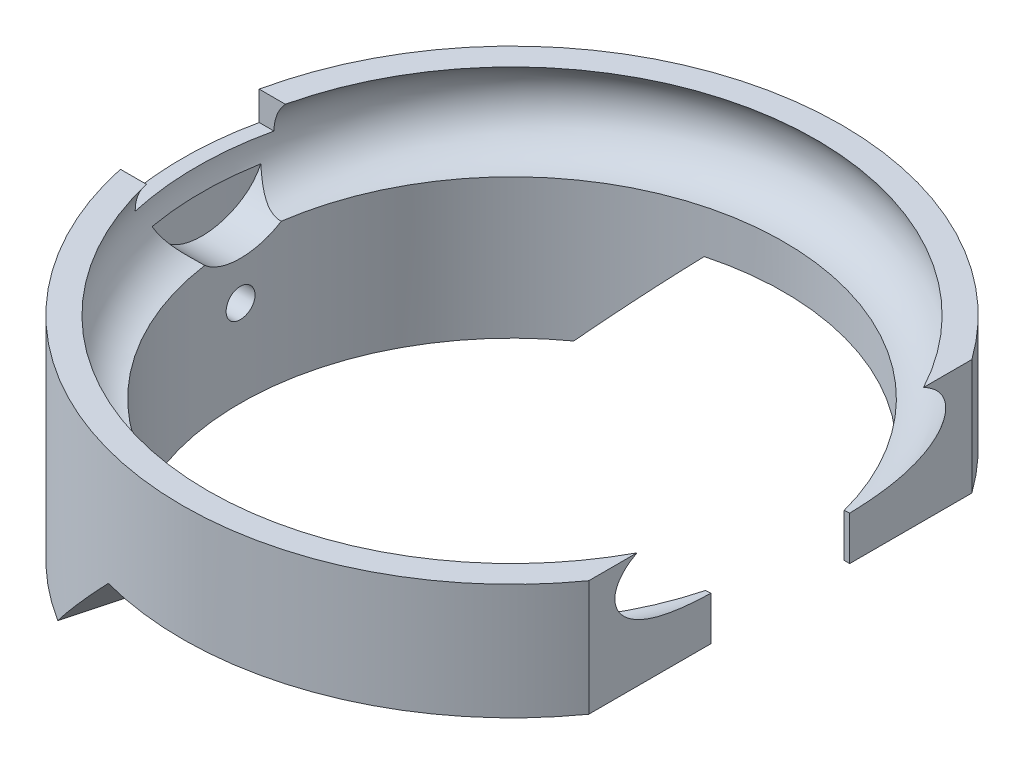
SolidWorks part; units mm, degrees
ref_plane "Alzado" through (0, 0, 0) normal (0, 0, 1) x (1, 0, 0)
ref_plane "Planta" through (0, 0, 0) normal (0, 1, 0) x (1, 0, 0)
ref_plane "Vista lateral" through (0, 0, 0) normal (1, 0, 0) x (0, 0, -1)
sketch "Croquis1" plane through (0, 0, 0) normal (0, 1, 0) x (1, 0, 0)
  circle A0 centre (0, 0) radius 17.1
  circle A1 centre (0, 0) radius 14.1
  dimension "D1" = 28.2
  dimension "D2" = 3
extrude "Saliente-Extruir1" add sketch "Croquis1" along normal mid plane 9
sketch "Croquis2" plane through (0, 4.5, 0) normal (0, 1, 0) x (1, 0, 0)
  line L1 (8.16, 3.6) -> (23.5806, 3.6)
  line L2 (8.16, 3.6) -> (8.16, -3.6)
  line L3 (8.16, -3.6) -> (23.5806, -3.6)
  line L4 (23.5806, 3.6) -> (23.5806, -3.6)
  point P4 (8.16, 0)
  dimension "D1" = 7.2
extrude "Cortar-Extruir1" cut sketch "Croquis2" against normal up to next
sketch "Croquis54" plane through (0, 0, 0) normal (0, 0, 1) x (1, 0, 0)
  line L0 (0, -13.582) -> (0, 13.1844) construction
  line L8 (-17.1, 4.5) -> (-17.1, -4.5) construction
  line L9 (-17.1, -9.5) -> (-14.1, -9.5)
  line L10 (-17.1, -9.5) -> (-17.1, 9.5)
  line L11 (-17.1, 9.5) -> (-14.1, 9.5)
  line L12 (-14.1, -9.5) -> (-14.1, 9.5)
  line L15 (16.7168, 4.5) -> (-17.1, 4.5) construction
  line L16 (-17.1, -4.5) -> (16.7168, -4.5) construction
  dimension "D1" = 3
  dimension "D2" = 5
  dimension "D3" = 5
revolve "Revolución1" add sketch "Croquis54" angle 150 mid plane about L0
sketch "Croquis12" plane through (0, 0, 0) normal (0, 1, 0) x (1, 0, 0)
  circle A0 centre (0, 0) radius 14.1
sweep "Cortar-Barrer2" cut path "Croquis12" circular profile diameter 4.5 parameters "D3"=4.5
chamfer "Chaflán3" distance 5 angle 45 4 edges at (-4.0376, -9.5, -15.0684) (-4.0376, 9.5, -15.0684) (-4.0376, -9.5, 15.0684) (-4.0376, 9.5, 15.0684)
sketch "Croquis61" plane through (0, 0, 0) normal (1, 0, 0) x (0, 0, -1)
  circle A0 centre (0, 0) radius 3
  dimension "D1" = 6
extrude "Cortar-Extruir2" cut sketch "Croquis61" against normal offset from surface (15.818 mm away) 1
sketch "Croquis62" plane through (0, 0, 0) normal (1, 0, 0) x (0, 0, -1)
  line L0 (-3.6, -1.5) -> (3.6, -1.5)
  line L1 (-20.6921, 12.3406) -> (19.3538, 12.3406)
  line L2 (-20.6921, 12.3406) -> (-20.6921, -12.7524)
  line L3 (-20.6921, -12.7524) -> (19.3538, -12.7524)
  line L4 (19.3538, 12.3406) -> (19.3538, -12.7524)
  line L7 (3.6, -1.5) -> (3.6, 1.5)
  line L8 (3.6, 1.5) -> (19.3538, 1.5)
  line L9 (-3.6, -1.5) -> (-3.6, 1.5)
  line L10 (-3.6, 1.5) -> (-20.6921, 1.5)
  line L11 (-20.6921, 0) -> (19.3538, 0) construction
  dimension "D1" = 1.5
  dimension "D2" = 1.5
  dimension "D3" = 1.5
extrude "Cortar-Extruir3" cut sketch "Croquis62" against normal through all both and the other way through all contours L9 L11 L7 L8 L4 L1 L2 L10
ref_plane "Plano1" through (-17.1, 0, 0) normal (-1, 0, 0) x (0, -1, 0)
sketch "Croquis63" plane through (-17.1, 0, 0) normal (-1, 0, 0) x (0, -1, 0)
  line L0 (0, 3.6) -> (0, -3.6) construction
  circle A0 centre (5, 0) radius 0.75
  dimension "D1" = 1.5
  dimension "D2" = 5
extrude "Cortar-Extruir4" cut sketch "Croquis63" against normal up to next
sketch "Croquis64" plane through (-17.1, 0, 0) normal (-1, 0, 0) x (0, -1, 0)
  circle A0 centre (5, 0) radius 1.25
  dimension "D1" = 2.5
extrude "Cortar-Extruir5" cut sketch "Croquis64" against normal blind 0.5
sketch "Croquis65" plane through (0, 1.5, 0) normal (0, 1, 0) x (1, 0, 0)
  line L1 (13.9168, 9.9365) -> (16.7168, 9.9365)
  line L2 (13.9168, 9.9365) -> (13.9168, -9.9365)
  line L3 (13.9168, -9.9365) -> (16.7168, -9.9365)
  line L4 (16.7168, 9.9365) -> (16.7168, -9.9365)
  arc A0 (16.7168, 3.6) -> (-16.7168, 3.6) centre (0, 0) ccw construction
  arc A1 (-16.7168, -3.6) -> (16.7168, -3.6) centre (0, 0) ccw construction
  point P4 (0, 0)
  point P9 (0, 0)
  dimension "D1" = 2.8
extrude "Cortar-Extruir6" cut sketch "Croquis65" against normal up to surface (6 mm away)
